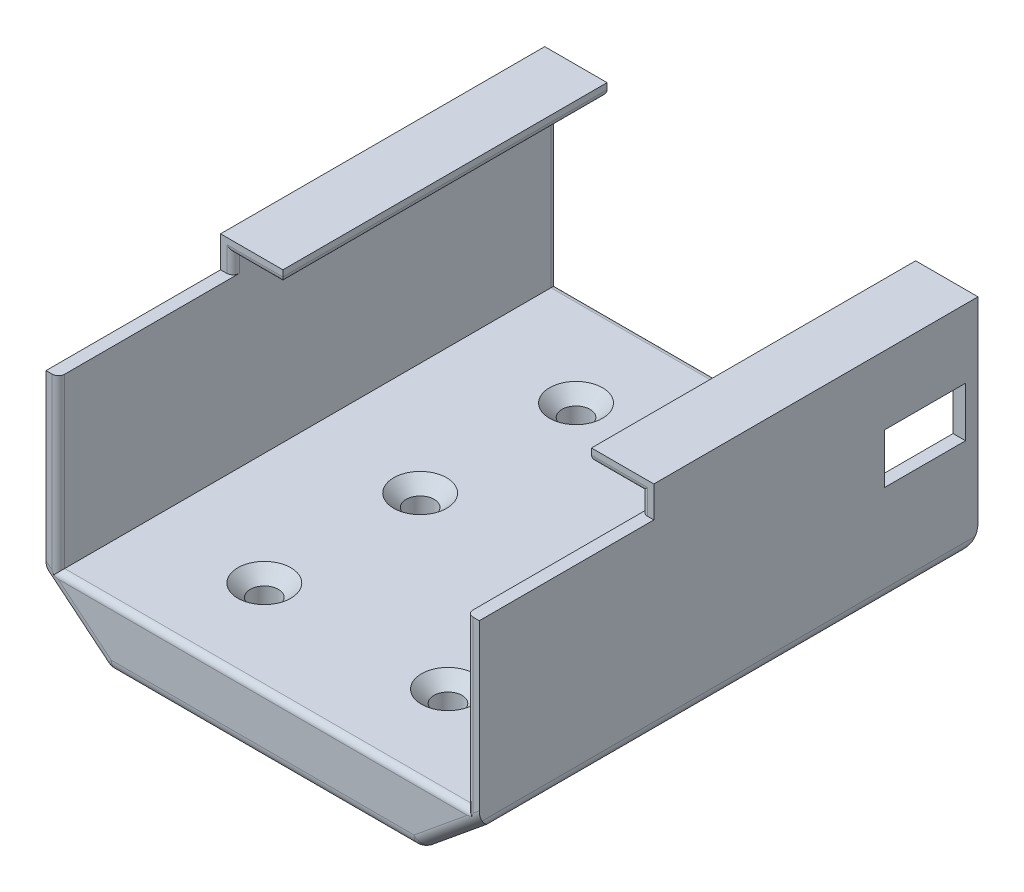
SolidWorks part; units mm, degrees
ref_plane "Front Plane" through (0, 0, 0) normal (0, 0, 1) x (1, 0, 0)
ref_plane "Top Plane" through (0, 0, 0) normal (0, 1, 0) x (1, 0, 0)
ref_plane "Right Plane" through (0, 0, 0) normal (1, 0, 0) x (0, 0, -1)
sketch "Sketch1" plane through (0, 0, 0) normal (0, 1, 0) x (1, 0, 0)
  line L1 (-25, 40) -> (25, 40)
  line L2 (-25, 40) -> (-25, -40)
  line L3 (-25, -40) -> (25, -40)
  line L4 (25, 40) -> (25, -40)
  line L5 (-25, 40) -> (25, -40) construction
  line L6 (-25, -40) -> (25, 40) construction
  point P0 (0, 0)
  dimension "D1" = 50
  dimension "D2" = 80
extrude "Boss-Extrude1" add sketch "Sketch1" along normal blind 10
sketch "Sketch2" plane through (0, 10, 0) normal (0, 1, 0) x (1, 0, 0)
  line L0 (0, 40) -> (0, -40) construction
  line L1 (25, 40) -> (-25, 40) construction
  line L2 (-25, -40) -> (25, -40) construction
  line L3 (-14.7304, 40) -> (-14.7304, -40) construction
  circle A0 centre (-14.7304, 0) radius 2.25
  circle A1 centre (-14.7304, 25) radius 2.25
  circle A2 centre (-14.7304, -25) radius 2.25
  circle A3 centre (14.7304, -25) radius 2.25
  circle A4 centre (14.7304, 0) radius 2.25
  circle A5 centre (14.7304, 25) radius 2.25
  dimension "D1" = 4.5
  dimension "D2" = 25
  dimension "D3" = 25
extrude "Cut-Extrude1" cut sketch "Sketch2" against normal through all
chamfer "Chamfer1" distance 2 angle 45 6 edges at (14.7304, 10, 22.75) (-14.7304, 10, 27.25) (-14.7304, 10, 2.25) (14.7304, 10, -2.25) (14.7304, 10, -27.25) (-14.7304, 10, -22.75)
sketch "Sketch3" plane through (0, 0, 0) normal (0, 0, 1) x (1, 0, 0)
  line L0 (0, 0) -> (0, 52.1179) construction
  line L1 (-25, 10) -> (-32.75, 10)
  line L2 (-32.75, 10) -> (-32.75, 40)
  line L3 (-32.75, 40) -> (-24.75, 40)
  line L4 (-24.75, 40) -> (-24.75, 42)
  line L5 (-24.75, 42) -> (-34.75, 42)
  line L6 (-34.75, 42) -> (-34.75, 8)
  line L7 (-34.75, 8) -> (-25, 0)
  line L8 (34.75, 8) -> (25, 0)
  line L9 (34.75, 42) -> (34.75, 8)
  line L10 (24.75, 42) -> (34.75, 42)
  line L11 (24.75, 40) -> (24.75, 42)
  line L12 (32.75, 40) -> (24.75, 40)
  line L13 (32.75, 10) -> (32.75, 40)
  line L14 (25, 10) -> (32.75, 10)
  line L15 (-25, 10) -> (-25, 0)
  line L16 (25, 10) -> (25, 0)
  dimension "D1" = 2
  dimension "D2" = 65.5
  dimension "D3" = 30
  dimension "D4" = 2
  dimension "D5" = 8
  dimension "D6" = 2
extrude "Boss-Extrude2" add sketch "Sketch3" along normal mid plane 80
sketch "Sketch4" plane through (0, 0, 0) normal (1, 0, 0) x (0, 0, -1)
  line L0 (-40, 42) -> (-12, 42)
  line L1 (-40, 42) -> (40, 42) construction
  line L2 (-12, 42) -> (-12, 37)
  line L3 (-12, 37) -> (-40, 37)
  line L4 (-40, 8) -> (-40, 42) construction
  line L5 (-40, 37) -> (-40, 42)
  dimension "D1" = 28
  dimension "D2" = 5
extrude "Cut-Extrude2" cut sketch "Sketch4" against normal through all both and the other way through all
sketch "Sketch5" plane through (34.75, 0, 0) normal (1, 0, 0) x (0, 0, -1)
  line L1 (25, 31) -> (38, 31)
  line L2 (25, 31) -> (25, 23)
  line L3 (25, 23) -> (38, 23)
  line L4 (38, 31) -> (38, 23)
extrude "Cut-Extrude3" cut sketch "Sketch5" against normal up to next
fillet "Fillet1" radius 1 14 edges at (28.75, 40, -40) (-28.75, 40, -40) (-32.75, 25, -40) (32.75, 25, -40) (0, 10, -40) (32.75, 23.5, 40) (0, 10, 40) (-32.75, 23.5, 40) (24.75, 40, -14) (-24.75, 40, -14) (-32.75, 38.5, 12) (32.75, 38.5, 12) (28.75, 40, 12) (-28.75, 40, 12)
fillet "Fillet2" radius 2 10 edges at (-29.875, 4, 40) (29.875, 4, -40) (0, 0, -40) (-29.875, 4, -40) (-34.75, 8, 0) (34.75, 8, 0) (29.875, 4, 40) (0, 0, 40) (25, 0, 0) (-25, 0, 0)
